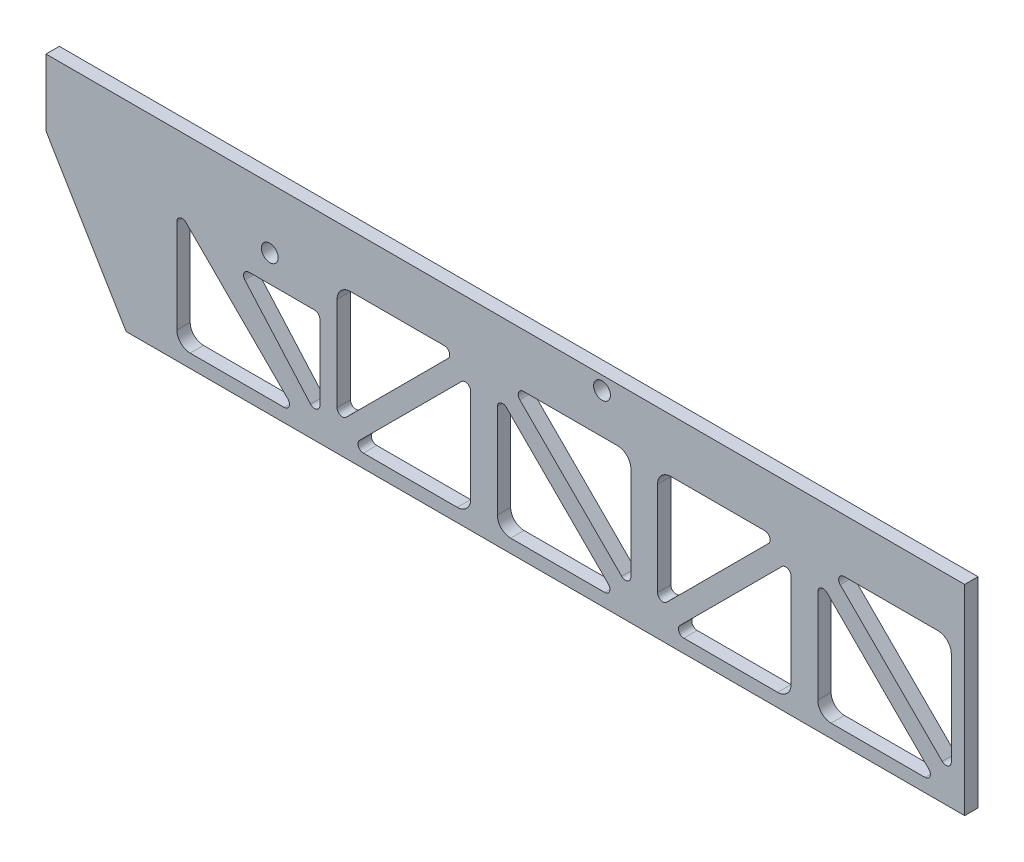
SolidWorks part; units mm, degrees
material "Pine"
ref_plane "Front Plane" through (0, 0, 0) normal (0, 0, 1) x (1, 0, 0)
ref_plane "Top Plane" through (0, 0, 0) normal (0, 1, 0) x (1, 0, 0)
ref_plane "Right Plane" through (0, 0, 0) normal (1, 0, 0) x (0, 0, -1)
sketch "Model" plane through (0, 0, 0) normal (0, 0, 1) x (1, 0, 0)
  line L0 (-306.6281, 15.625) -> (-306.6281, 51.1493)
  line L1 (-309.1681, 53.6893) -> (-340.406, 53.6893)
  line L2 (-342.3135, 49.472) -> (-311.0755, 13.9477)
  line L8 (-171.2321, 6.35) -> (-215.9, 6.35)
  line L9 (-222.25, 57.3679) -> (-222.25, 12.7)
  line L10 (-217.9139, 59.1639) -> (-169.4361, 10.6861)
  line L11 (-234.95, 57.3679) -> (-234.95, 12.7)
  line L12 (-241.3, 6.35) -> (-285.9679, 6.35)
  line L13 (-239.2861, 59.1639) -> (-287.7639, 10.6861)
  line L14 (-294.1139, 17.0361) -> (-245.6361, 65.5139)
  line L15 (-298.45, 63.5) -> (-298.45, 18.8321)
  line L16 (-247.4321, 69.85) -> (-292.1, 69.85)
  line L17 (-323.6321, 6.35) -> (-368.3, 6.35)
  line L18 (-374.65, 57.3679) -> (-374.65, 12.7)
  line L19 (-370.3139, 59.1639) -> (-321.8361, 10.6861)
  line L20 (-18.8321, 6.35) -> (-63.5, 6.35)
  line L21 (-69.85, 57.3679) -> (-69.85, 12.7)
  line L22 (-17.0361, 10.6861) -> (-65.5139, 59.1639)
  line L23 (-82.55, 57.3679) -> (-82.55, 12.7)
  line L24 (-88.9, 6.35) -> (-133.5679, 6.35)
  line L25 (-86.8861, 59.1639) -> (-135.3639, 10.6861)
  line L26 (-93.2361, 65.5139) -> (-141.7139, 17.0361)
  line L27 (-146.05, 63.5) -> (-146.05, 18.8321)
  line L28 (-95.0321, 69.85) -> (-139.7, 69.85)
  line L29 (-163.0861, 17.0361) -> (-211.5639, 65.5139)
  line L30 (-165.1, 69.85) -> (-209.7679, 69.85)
  line L31 (-158.75, 63.5) -> (-158.75, 18.8321)
  line L35 (-398.78, 0) -> (-436.88, 63.5)
  line L36 (0, 0) -> (-398.78, 0)
  line L37 (0, 0) -> (0, 95.25)
  line L38 (0, 95.25) -> (-436.88, 95.25)
  line L39 (-436.88, 63.5) -> (-436.88, 95.25)
  line L40 (-6.35, 63.5) -> (-6.35, 18.8321)
  line L41 (-59.1639, 65.5139) -> (-10.6861, 17.0361)
  line L42 (-12.7, 69.85) -> (-57.3679, 69.85)
  arc A0 (-222.25, 12.7) -> (-215.9, 6.35) centre (-215.9, 12.7) ccw
  arc A1 (-217.9139, 59.1639) -> (-222.25, 57.3679) centre (-219.71, 57.3679) ccw
  arc A2 (-171.2321, 6.35) -> (-169.4361, 10.6861) centre (-171.2321, 8.89) ccw
  arc A3 (-234.95, 57.3679) -> (-239.2861, 59.1639) centre (-237.49, 57.3679) ccw
  arc A4 (-241.3, 6.35) -> (-234.95, 12.7) centre (-241.3, 12.7) ccw
  arc A5 (-287.7639, 10.6861) -> (-285.9679, 6.35) centre (-285.9679, 8.89) ccw
  arc A6 (-245.6361, 65.5139) -> (-247.4321, 69.85) centre (-247.4321, 67.31) ccw
  arc A7 (-298.45, 18.8321) -> (-294.1139, 17.0361) centre (-295.91, 18.8321) ccw
  arc A8 (-292.1, 69.85) -> (-298.45, 63.5) centre (-292.1, 63.5) ccw
  arc A9 (-323.6321, 6.35) -> (-321.8361, 10.6861) centre (-323.6321, 8.89) ccw
  arc A10 (-374.65, 12.7) -> (-368.3, 6.35) centre (-368.3, 12.7) ccw
  arc A11 (-370.3139, 59.1639) -> (-374.65, 57.3679) centre (-372.11, 57.3679) ccw
  arc A12 (-69.85, 12.7) -> (-63.5, 6.35) centre (-63.5, 12.7) ccw
  arc A13 (-65.5139, 59.1639) -> (-69.85, 57.3679) centre (-67.31, 57.3679) ccw
  arc A14 (-18.8321, 6.35) -> (-17.0361, 10.6861) centre (-18.8321, 8.89) ccw
  arc A15 (-82.55, 57.3679) -> (-86.8861, 59.1639) centre (-85.09, 57.3679) ccw
  arc A16 (-88.9, 6.35) -> (-82.55, 12.7) centre (-88.9, 12.7) ccw
  arc A17 (-135.3639, 10.6861) -> (-133.5679, 6.35) centre (-133.5679, 8.89) ccw
  arc A18 (-93.2361, 65.5139) -> (-95.0321, 69.85) centre (-95.0321, 67.31) ccw
  arc A19 (-146.05, 18.8321) -> (-141.7139, 17.0361) centre (-143.51, 18.8321) ccw
  arc A20 (-139.7, 69.85) -> (-146.05, 63.5) centre (-139.7, 63.5) ccw
  arc A21 (-163.0861, 17.0361) -> (-158.75, 18.8321) centre (-161.29, 18.8321) ccw
  arc A22 (-209.7679, 69.85) -> (-211.5639, 65.5139) centre (-209.7679, 67.31) ccw
  arc A23 (-158.75, 63.5) -> (-165.1, 69.85) centre (-165.1, 63.5) ccw
  arc A24 (-306.6281, 15.625) -> (-311.0755, 13.9477) centre (-309.1681, 15.625) cw
  arc A25 (-340.406, 53.6893) -> (-342.3135, 49.472) centre (-340.406, 51.1493) ccw
  arc A26 (-306.6281, 51.1493) -> (-309.1681, 53.6893) centre (-309.1681, 51.1493) ccw
  arc A27 (-10.6861, 17.0361) -> (-6.35, 18.8321) centre (-8.89, 18.8321) ccw
  arc A28 (-57.3679, 69.85) -> (-59.1639, 65.5139) centre (-57.3679, 67.31) ccw
  arc A29 (-6.35, 63.5) -> (-12.7, 69.85) centre (-12.7, 63.5) ccw
  circle A30 centre (-172.466, 88.9) radius 4
  circle A31 centre (-330.454, 66.548) radius 4
  dimension "D2" = 172.466
  dimension "D4" = 8
  dimension "D5" = 157.988
  dimension "D7" = 8
  dimension "D6" = 22.352
  dimension "D8" = 2.54
  dimension "D1" = 95.25
  dimension "D3" = 6.35
extrude "Boss-Extrude1" add sketch "Model" along normal blind 6.35
equation "\"thick\"=0.25"
equation "\"D1@Boss-Extrude1\"=\"thick\""
